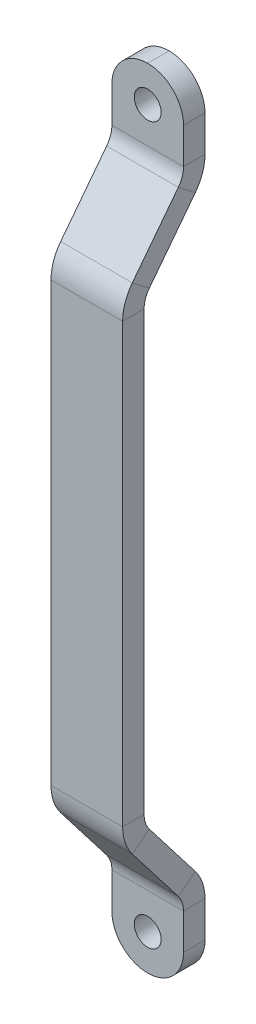
SolidWorks part; units mm, degrees
ref_plane "Front Plane" through (0, 0, 0) normal (0, 0, 1) x (1, 0, 0)
ref_plane "Top Plane" through (0, 0, 0) normal (0, 1, 0) x (1, 0, 0)
ref_plane "Right Plane" through (0, 0, 0) normal (1, 0, 0) x (0, 0, -1)
sketch "Sketch6" plane through (0, 0, 0) normal (0, 1, 0) x (1, 0, 0)
  line L1 (0, 0) -> (10, 0)
  line L2 (0, 0) -> (0, -3)
  line L3 (0, -3) -> (10, -3)
  line L4 (10, 0) -> (10, -3)
  dimension "D1" = 3
  dimension "D2" = 10
sketch "Sketch7" plane through (0, 0, 0) normal (1, 0, 0) x (0, 0, -1)
  line L0 (-1.5, 0) -> (-1.5, 10)
  line L1 (0, 0) -> (-3, 0) construction
  line L2 (-2.5392, 13.0516) -> (-8.9608, 21.3863)
  line L3 (-10, 24.4379) -> (-10, 55)
  arc A0 (-1.5, 10) -> (-2.5392, 13.0516) centre (-6.5, 10) ccw
  arc A1 (-8.9608, 21.3863) -> (-10, 24.4379) centre (-5, 24.4379) cw
  dimension "D1" = 5
  dimension "D2" = 10
  dimension "D3" = 55
sweep "Sweep1" add profiles "Sketch6" path "Sketch7"
mirror "Mirror2" about plane through (0, 55, 8.5) normal (0, 1, 0) of bodies 107
sketch "Sketch8" plane through (0, 0, 0) normal (0, 0, -1) x (-1, 0, 0)
  line L0 (-10, 55) -> (0, 55)
  line L1 (-10, 24.4379) -> (-10, 85.5621) construction
  line L2 (0, 24.4379) -> (0, 85.5621) construction
  line L3 (-5, 5) -> (-5, 105) construction
  circle A0 centre (-5, 5) radius 1.875
  circle A1 centre (-5, 105) radius 1.875
  point P10 (-5, 55)
  dimension "D1" = 3.75
  dimension "D2" = 3.75
  dimension "D3" = 100
extrude "Cut-Extrude2" cut sketch "Sketch8" against normal through all contours A1 | A0 region at (5, 105, 0)
fillet "Fillet1" radius 5 4 edges at (0, 0, 1.5) (10, 0, 1.5) (10, 110, 1.5) (0, 110, 1.5)
